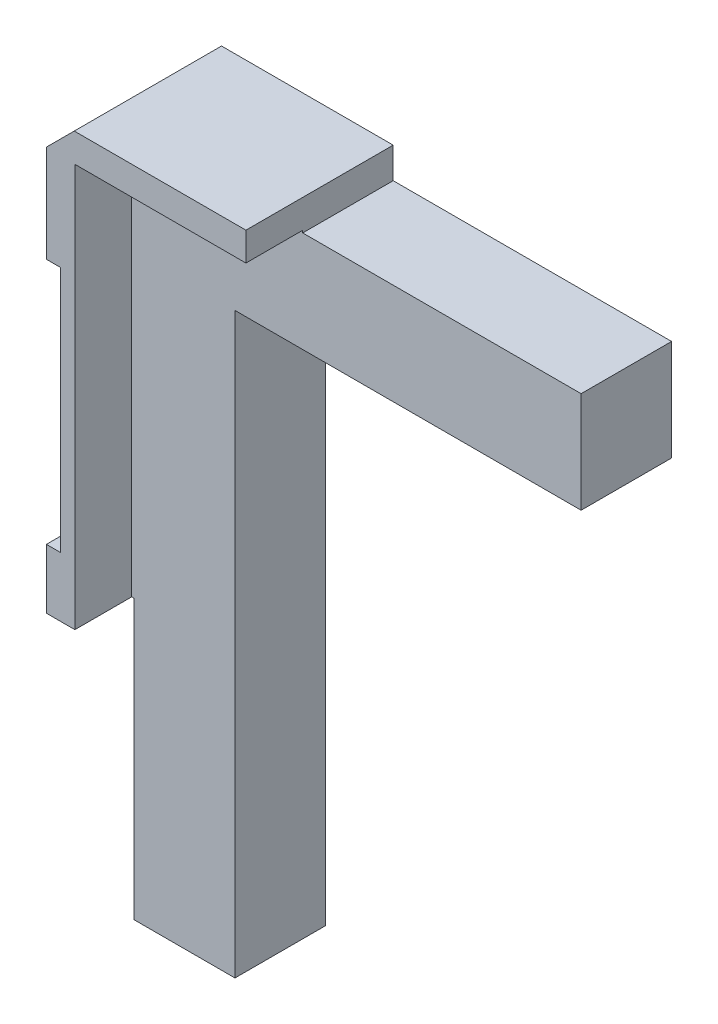
SolidWorks part; units mm, degrees
ref_plane "Front Plane" through (0, 0, 0) normal (0, 0, 1) x (1, 0, 0)
ref_plane "Top Plane" through (0, 0, 0) normal (0, 1, 0) x (1, 0, 0)
ref_plane "Right Plane" through (0, 0, 0) normal (1, 0, 0) x (0, 0, -1)
ref_plane "PZ 20.375" through (0, 0, 20.375) normal (0, 0, 1) x (1, 0, 0)
sketch "body and tongues sketch" plane through (0, 0, 20.375) normal (0, 0, 1) x (1, 0, 0)
  line L0 (-3.42, 3.07) -> (-0.42, 6.07)
  line L1 (-0.42, 6.07) -> (18.08, 6.07)
  line L2 (18.08, 6.07) -> (18.08, 2.75)
  line L3 (18.08, 2.75) -> (48.08, 2.75)
  line L4 (48.08, 2.75) -> (48.08, -8.13)
  line L5 (48.08, -8.13) -> (10.78, -8.13)
  line L6 (10.78, -8.13) -> (10.78, -70.43)
  line L7 (10.78, -70.43) -> (-0.1, -70.43)
  line L8 (-0.1, -70.43) -> (-0.1, -40.43)
  line L9 (-0.1, -40.43) -> (-3.42, -40.43)
  line L10 (-3.42, -40.43) -> (-3.42, 3.07)
extrude "body and tongues" add sketch "body and tongues sketch" along normal mid plane 9.75
ref_plane "PZ 23.435" through (0, 0, 23.435) normal (0, 0, 1) x (1, 0, 0)
sketch "rim sketch" plane through (0, 0, 23.435) normal (0, 0, 1) x (1, 0, 0)
  line L0 (-3.42, 3.07) -> (-0.42, 6.07)
  line L1 (-0.42, 6.07) -> (18.08, 6.07)
  line L2 (18.08, 6.07) -> (18.08, 3)
  line L3 (18.08, 3) -> (-0.35, 3)
  line L4 (-0.35, 3) -> (-0.35, -40.43)
  line L5 (-0.35, -40.43) -> (-3.42, -40.43)
  line L6 (-3.42, -40.43) -> (-3.42, 3.07)
extrude "rim" add sketch "rim sketch" along normal mid plane 15.87
sketch "bracket seat sketch" plane through (0, 0, 23.435) normal (0, 0, 1) x (1, 0, 0)
  line L0 (-1.92, -34) -> (-4.42, -34)
  line L1 (-4.42, -34) -> (-4.42, -7.4)
  line L2 (-4.42, -7.4) -> (-1.92, -7.4)
  line L3 (-1.92, -7.4) -> (-1.92, -34)
extrude "bracket seat" cut sketch "bracket seat sketch" against normal mid plane 17.87
ref_plane "PX 2.580" through (2.58, 0, 0) normal (1, 0, 0) x (0, 0, -1)
sketch "screw pilots sketch" plane through (2.58, 0, 0) normal (1, 0, 0) x (0, 0, -1)
  circle A0 centre (-20.375, -28.7) radius 1.35
  circle A1 centre (-20.375, -12.7) radius 1.35
extrude "screw pilots" cut sketch "screw pilots sketch" against normal mid plane 11
equation "\"diffL\" = 608.8mm"
equation "\"diffW\" = 329.4mm"
equation "\"diffT\" = 2.9mm"
equation "\"chanSlotW\" = 12.9mm"
equation "\"chanSlotDepth\" = 11.13mm"
equation "\"chanFloor\" = 1.57mm"
equation "\"chanLeg\" = 12.7mm"
equation "\"lightL\" = 605mm"
equation "\"lightW\" = 331mm"
equation "\"lightH\" = 92mm"
equation "\"lightSideFlat\" = 30mm"
equation "\"lightSlopeLen\" = 33.1mm"
equation "\"lightWingDepth\" = 47.9mm"
equation "\"lightWingFlat\" = 90.2mm"
equation "\"lightChanW\" = 99.6mm"
equation "\"lightChanStand\" = 44.1mm"
equation "\"insFlangeD\" = 12.3mm"
equation "\"insFromEnd\" = 20.7mm"
equation "\"insUpSlope\" = 20.8mm"
equation "\"gaugeH\" = 10mm"
equation "\"gaugeStepLen\" = 14mm"
equation "\"gaugeStepW0\" = 13.1mm"
equation "\"gaugeStepDW\" = 0.2mm"
equation "\"gaugeSteps\" = 5mm"
equation "\"gaugeHandleLen\" = 30mm"
equation "\"gaugeHandleW\" = 24mm"
equation "\"gaugeSlot0\" = 3mm"
equation "\"gaugeSlotD\" = 0.1mm"
equation "\"gaugeSlotDepth\" = 8mm"
equation "\"gap\" = 25.4mm"
equation "\"edgeL\" = 1mm"
equation "\"edgeW\" = 0.75mm"
equation "\"proud\" = 1.5mm"
equation "\"seatClr\" = 0.15mm"
equation "\"tongueClrZ\" = 0.1mm"
equation "\"tongueClrX\" = 0.25mm"
equation "\"tongueLen\" = 30mm"
equation "\"armSide\" = 45mm"
equation "\"armEnd\" = 20mm"
equation "\"cornerCham\" = 3mm"
equation "\"brkW\" = 26mm"
equation "\"brkT\" = 7mm"
equation "\"brkSeatClr\" = 0.2mm"
equation "\"brkScrewSpan\" = 16mm"
equation "\"pilotD\" = 2.7mm"
equation "\"pilotDepth\" = 10mm"
equation "\"screwClrD\" = 3.9mm"
equation "\"jogBelow\" = 4mm"
equation "\"padT\" = 7mm"
equation "\"padLen\" = 31mm"
equation "\"m6Clr\" = 7mm"
equation "\"m6Slot\" = 3mm"
equation "\"flangeRelD\" = 17mm"
equation "\"flangeRelDepth\" = 1.5mm"
equation "\"relLen\" = 7mm"
equation "\"relDepth\" = 4mm"
equation "\"relLand\" = 2mm"
equation "\"knockN\" = 100mm"
equation "\"petgcfE\" = 3000mm"
equation "\"mockExtent\" = 110mm"
equation "\"relZnear\" = 9.4mm"
equation "\"relZfar\" = 23.4mm"
equation "\"headD\" = 8mm"
equation "\"headH\" = 2.5mm"
equation "\"headFromEnd\" = 6.8mm"
equation "\"headBack\" = 16.4mm"
equation "\"sideClr\" = 0.4mm"
